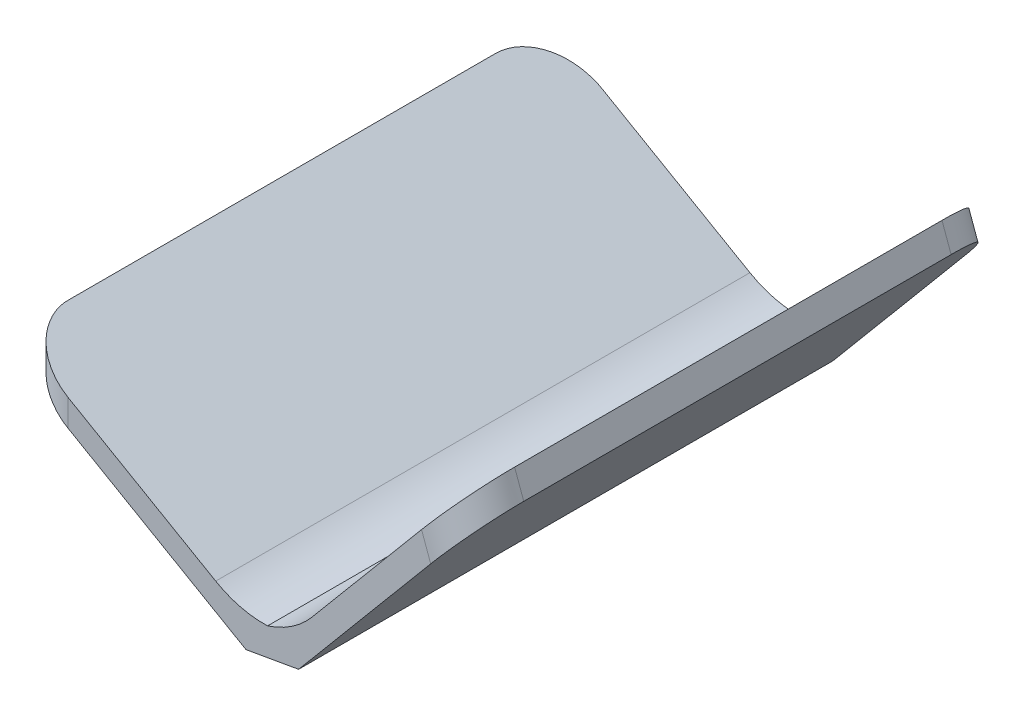
SolidWorks part; units mm, degrees
ref_plane "Front Plane" through (0, 0, 0) normal (0, 0, 1) x (1, 0, 0)
ref_plane "Top Plane" through (0, 0, 0) normal (0, 1, 0) x (1, 0, 0)
ref_plane "Right Plane" through (0, 0, 0) normal (1, 0, 0) x (0, 0, -1)
sketch "Sketch1" plane through (0, 0, 0) normal (0, 0, 1) x (1, 0, 0)
  line L0 (-43.6646, 6.4464) -> (-11.5253, 44.7487)
  line L1 (-51.8026, 5.0115) -> (-43.6646, 6.4464)
  line L3 (-51.8026, 0.0115) -> (-41.9545, 1.748)
  line L5 (-11.5253, 44.7487) -> (-9.8152, 40.0502)
  line L6 (-9.8152, 40.0502) -> (-41.9545, 1.748)
  line L8 (-51.8026, 5.0115) -> (-95.1039, 30.0115)
  line L9 (-95.1039, 30.0115) -> (-95.1039, 25.0115)
  line L10 (-95.1039, 25.0115) -> (-51.8026, 0.0115)
  dimension "D1" = 10
  dimension "D2" = 140
  dimension "D4" = 5
  dimension "D5" = 5
  dimension "D6" = 4.3301
  dimension "D7" = 4.3301
  dimension "D10" = 140
extrude "Boss-Extrude2" add sketch "Sketch1" along normal blind 100 contours L1 L0 L5 L6 L3 L10 L9 L8
fillet "Fillet1" radius 10 4 edges at (-95.1039, 27.5115, 0) (-10.6702, 42.3994, 0) (-10.6702, 42.3994, 100) (-95.1039, 27.5115, 100)
fillet "Fillet7" radius 18 2 edges at (-51.8026, 5.0115, 50) (-43.6646, 6.4464, 50)
